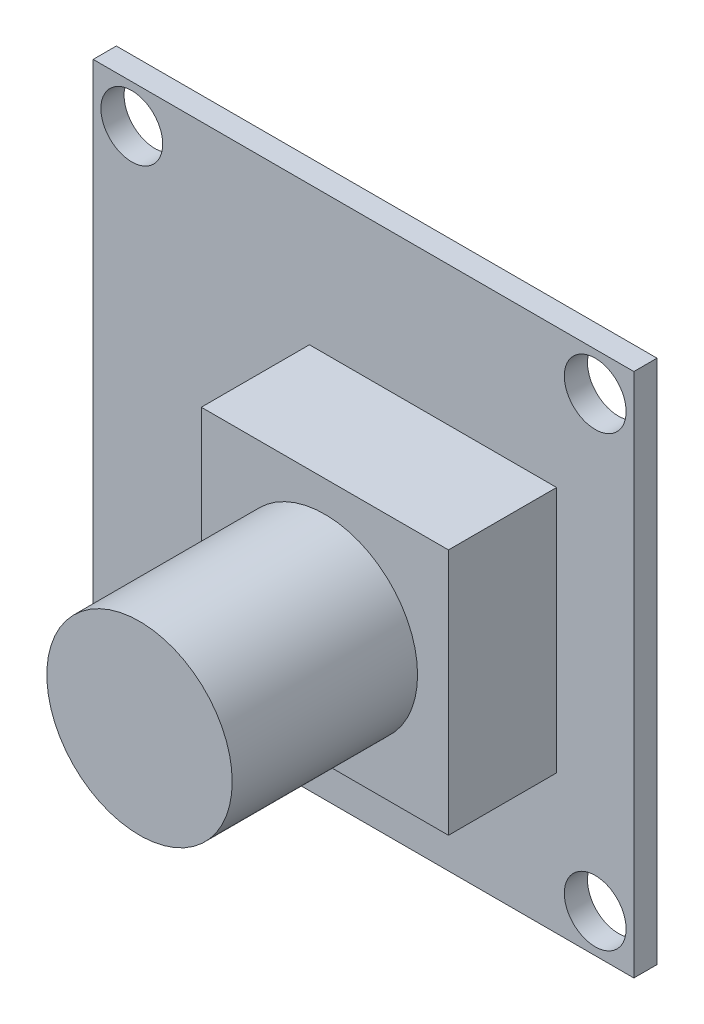
SolidWorks part; units mm, degrees
ref_plane "Front Plane" through (0, 0, 0) normal (0, 0, 1) x (1, 0, 0)
ref_plane "Top Plane" through (0, 0, 0) normal (0, 1, 0) x (1, 0, 0)
ref_plane "Right Plane" through (0, 0, 0) normal (1, 0, 0) x (0, 0, -1)
sketch "Sketch1" plane through (0, 0, 0) normal (0, 0, 1) x (1, 0, 0)
  line L1 (-17.5, 17) -> (17.5, 17)
  line L2 (-17.5, 17) -> (-17.5, -17)
  line L3 (-17.5, -17) -> (17.5, -17)
  line L4 (17.5, 17) -> (17.5, -17)
  line L5 (-17.5, 17) -> (17.5, -17) construction
  line L6 (-17.5, -17) -> (17.5, 17) construction
  point P0 (0, 0)
  dimension "D1" = 34
  dimension "D2" = 35
extrude "Boss-Extrude1" add sketch "Sketch1" against normal blind 1.5 contours L4 L3 L2 L1
sketch "Sketch2" plane through (0, 0, 0) normal (0, 0, 1) x (1, 0, 0)
  line L0 (-17.5, -17) -> (17.5, -17) construction
  line L2 (-17.5, 17) -> (-17.5, -17) construction
  line L3 (0, -55) -> (0, 55) construction
  line L4 (55, 0) -> (-55, 0) construction
  circle A0 centre (-15, -14.5) radius 2
  circle A1 centre (15, -14.5) radius 2
  circle A2 centre (15, 14.5) radius 2
  circle A3 centre (-15, 14.5) radius 2
  dimension "D1" = 4
  dimension "D2" = 2.5
  dimension "D3" = 2.5
extrude "Cut-Extrude1" cut sketch "Sketch2" against normal up to next
sketch "Sketch3" plane through (0, 0, 0) normal (0, 0, 1) x (1, 0, 0)
  line L0 (-3.5, 8) -> (12.5, 8)
  line L1 (12.5, 8) -> (12.5, -8)
  line L2 (12.5, -8) -> (-3.5, -8)
  line L3 (-3.5, -8) -> (-3.5, 8)
  line L4 (17.5, 17) -> (17.5, -17) construction
  line L5 (-17.5, 17) -> (17.5, 17) construction
  dimension "D1" = 16
  dimension "D2" = 16
  dimension "D3" = 5
  dimension "D4" = 9
extrude "Boss-Extrude3" add sketch "Sketch3" along normal blind 7
ref_plane "Plane1" through (0, 0, 7) normal (0, 0, 1) x (1, 0, 0)
sketch "Sketch4" plane through (0, 0, 7) normal (0, 0, 1) x (1, 0, 0)
  line L0 (-3.5, 0) -> (12.5, 0) construction
  line L1 (-3.5, 8) -> (-3.5, -8) construction
  line L2 (12.5, -8) -> (12.5, 8) construction
  line L3 (4.5, 8) -> (4.5, -8) construction
  line L4 (12.5, 8) -> (-3.5, 8) construction
  line L5 (-3.5, -8) -> (12.5, -8) construction
  circle A0 centre (4.5, 0) radius 6
  dimension "D1" = 12
extrude "Boss-Extrude4" add sketch "Sketch4" along normal blind 12
ref_plane "Plane2" through (0, 0, 19) normal (0, 0, 1) x (1, 0, 0)
sketch "Sketch5" plane through (0, 0, 19) normal (0, 0, 1) x (1, 0, 0)
  point P0 (4.5, 0)
sketch "Sketch6" plane through (0, 0, 0) normal (0, 0, 1) x (1, 0, 0)
  point P0 (4.5, 0)
sketch3d "3DSketch2"
  line L0 (4.5, 0, 19) -> (4.5, 0, -49981) construction
